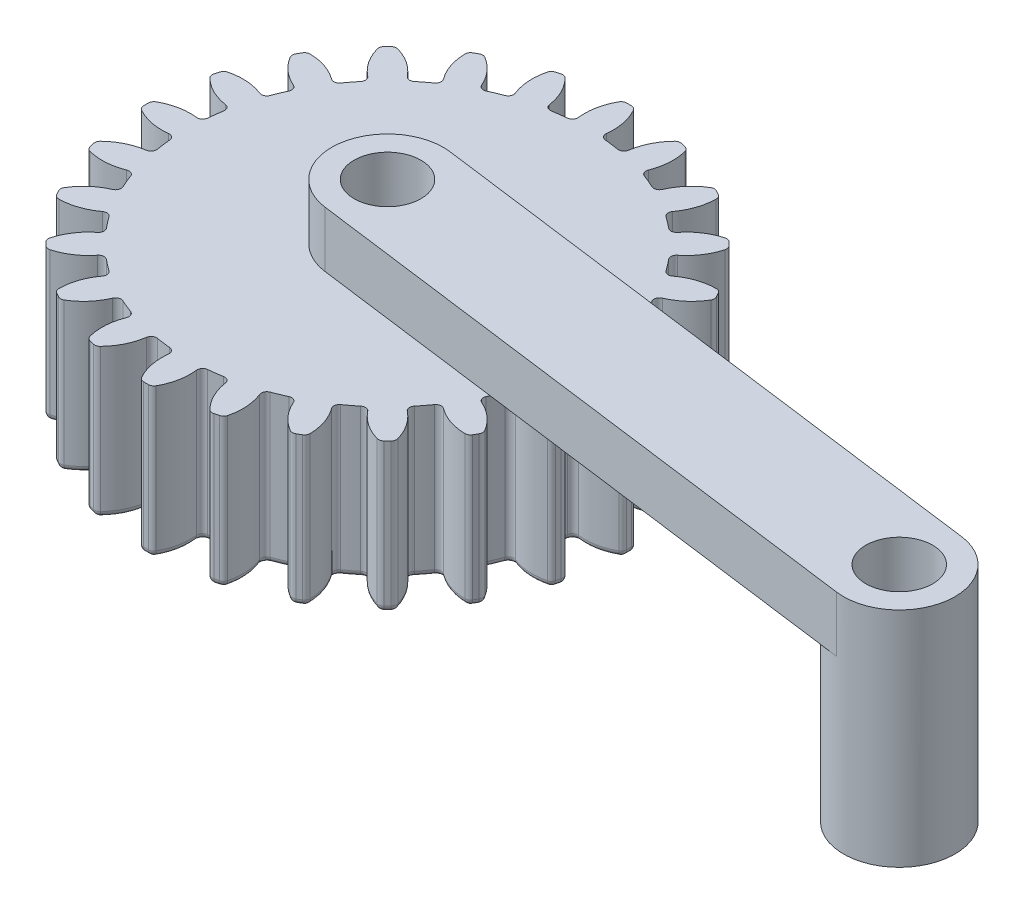
SolidWorks part; units mm, degrees
note: The reader was unsure of these and kept them because the rebuilt part matched: shared geometry of "Sketch2<5>".
ref_plane "Front Plane" through (0, 0, 0) normal (0, 0, 1) x (1, 0, 0)
ref_plane "Top Plane" through (0, 0, 0) normal (0, 1, 0) x (1, 0, 0)
ref_plane "Right Plane" through (0, 0, 0) normal (1, 0, 0) x (0, 0, -1)
sketch "Sketch2" plane through (0, 0, 0) normal (0, 1, 0) x (1, 0, 0)
  line L0 (0, 0) -> (0, 10.4648) construction
  line L1 (0.3, 13) -> (-0.3, 13)
  circle A0 centre (0, 0) radius 10.75
  circle A1 centre (0, 0) radius 13 construction
  arc A2 (-0.3, 13) -> (-0.7, 10.7272) centre (2.2248, 11.3841) ccw
  arc A3 (0.3, 13) -> (0.7, 10.7272) centre (-2.2248, 11.3841) cw
  circle A4 centre (0, 0) radius 2.55
  arc A5 (-0.7, 10.7272) -> (0.7, 10.7272) centre (0, 0) cw
  point P10 (0, 13)
  dimension "D1" = 21.5
  dimension "D2" = 26
  dimension "D5" = 5.1
  dimension "D3" = 0.6
  dimension "D4" = 0.7
extrude "Boss-Extrude1" add sketch "Sketch2" along normal blind 8
extrude "Boss-Extrude2" add sketch "Sketch2<5>" along normal blind 8 contours A3 L1 A2 A0
sketch "Sketch2<5>" plane through (0, 0, 0) normal (0, 1, 0) x (1, 0, 0) same geometry as "Sketch2"
pattern_circular "CirPattern2" count 24 over 360 about axis through (0, 0, 0) along (0, 1, 0) of "Boss-Extrude2"
sketch "Sketch3" plane through (0, 8, 0) normal (0, 1, 0) x (1, 0, 0)
  line L0 (31.7262, -4.1768) -> (0, 0) construction
  line L1 (31.3347, -7.1512) -> (-0.3916, -2.9743)
  line L2 (32.1178, -1.2025) -> (0.3916, 2.9743)
  line L3 (0, 0) -> (16.4404, 0) construction
  line L4 (0, 0) -> (14.8691, -3.9842) construction
  line L5 (12.4794, -3.6544) -> (12.6347, -3.0749) construction
  line L6 (12.6347, -3.0749) -> (12.557, -3.3646) construction
  arc A0 (31.3347, -7.1512) -> (32.1178, -1.2025) centre (31.7262, -4.1768) ccw
  arc A1 (0.3916, 2.9743) -> (-0.3916, -2.9743) centre (0, 0) ccw
  circle A2 centre (0, 0) radius 1.8
  circle A3 centre (31.7262, -4.1768) radius 1.8
  point P2 (15.8631, -2.0884)
  dimension "D1" = 3
  dimension "D3" = 3.6
  dimension "D2" = 32
  dimension "D4" = 15
  dimension "D5" = 7.5
extrude "Boss-Extrude3" add sketch "Sketch3" along normal blind 3
sketch "Sketch4" plane through (0, 8, 0) normal (0, -1, 0) x (1, 0, 0)
  circle A0 centre (31.7262, 4.1768) radius 1.8
  circle A1 centre (31.7262, 4.1768) radius 3
  dimension "D1" = 3.6
extrude "Boss-Extrude4" add sketch "Sketch4" along normal blind 9
sketch "Sketch5" plane through (0, 8, 0) normal (0, -1, 0) x (1, 0, 0)
  circle A0 centre (0, 0) radius 1.8
  circle A1 centre (0, 0) radius 2.55
  dimension "D1" = 3.6
extrude "Boss-Extrude5" add sketch "Sketch5" along normal blind 3
fillet "Fillet1" radius 0.3 96 edges at (4.7574, 4, 9.64) (6.2402, 4, 11.4083) (6.7598, 4, 11.1083) (5.9698, 4, 8.94) (2.1003, 4, 10.5428) (3.0749, 4, 12.6347) (3.6544, 4, 12.4794) (3.4525, 4, 10.1805) (-0.7, 4, 10.7272) (-0.3, 4, 13) (0.3, 4, 13) (0.7, 4, 10.7272) (0.7, 4, -10.7272) (-3.4525, 4, 10.1805) (-3.6544, 4, 12.4794) (-3.0749, 4, 12.6347) (-2.1003, 4, 10.5428) (0.3, 4, -13) (-0.3, 4, -13) (-5.9698, 4, 8.94) (-6.7598, 4, 11.1083) (-6.2402, 4, 11.4083) (-4.7574, 4, 9.64) (-0.7, 4, -10.7272) (-8.0802, 4, 7.0903) (-9.4045, 4, 8.9803) (-8.9803, 4, 9.4045) (-7.0903, 4, 8.0802) (-9.64, 4, 4.7574) (-11.4083, 4, 6.2402) (-11.1083, 4, 6.7598) (-8.94, 4, 5.9698) (-10.5428, 4, 2.1003) (-12.6347, 4, 3.0749) (-12.4794, 4, 3.6544) (-10.1805, 4, 3.4525) (-10.7272, 4, -0.7) (-13, 4, -0.3) (-13, 4, 0.3) (-10.7272, 4, 0.7) (-10.1805, 4, -3.4525) (-12.4794, 4, -3.6544) (-12.6347, 4, -3.0749) (-10.5428, 4, -2.1003) (-8.94, 4, -5.9698) (-11.1083, 4, -6.7598) (-11.4083, 4, -6.2402) (-9.64, 4, -4.7574) (-7.0903, 4, -8.0802) (-8.9803, 4, -9.4045) (-9.4045, 4, -8.9803) (-8.0802, 4, -7.0903) (-4.7574, 4, -9.64) (-6.2402, 4, -11.4083) (-6.7598, 4, -11.1083) (-5.9698, 4, -8.94) (10.7272, 4, 0.7) (13, 4, 0.3) (13, 4, -0.3) (10.7272, 4, -0.7) (10.5428, 4, -2.1003) (12.6347, 4, -3.0749) (12.4794, 4, -3.6544) (10.1805, 4, -3.4525) (9.64, 4, -4.7574) (11.4083, 4, -6.2402) (11.1083, 4, -6.7598) (8.94, 4, -5.9698) (8.0802, 4, -7.0903) (9.4045, 4, -8.9803) (8.9803, 4, -9.4045) (7.0903, 4, -8.0802) (5.9698, 4, -8.94) (6.7598, 4, -11.1083) (6.2402, 4, -11.4083) (4.7574, 4, -9.64) (3.4525, 4, -10.1805) (3.6544, 4, -12.4794) (3.0749, 4, -12.6347) (2.1003, 4, -10.5428) (-2.1003, 4, -10.5428) (-3.0749, 4, -12.6347) (-3.6544, 4, -12.4794) (-3.4525, 4, -10.1805) (10.1805, 4, 3.4525) (12.4794, 4, 3.6544) (12.6347, 4, 3.0749) (10.5428, 4, 2.1003) (8.94, 4, 5.9698) (11.1083, 4, 6.7598) (11.4083, 4, 6.2402) (9.64, 4, 4.7574) (7.0903, 4, 8.0802) (8.9803, 4, 9.4045) (9.4045, 4, 8.9803) (8.0802, 4, 7.0903)
fillet "Fillet2" radius 0.3 192 edges at (-4.6982, 0, 9.7715) (-3.5874, 0, 10.2316) (-2.009, 0, 10.6545) (-0.817, 0, 10.8115) (0.817, 0, 10.8115) (2.009, 0, 10.6545) (3.5874, 0, 10.2316) (4.6982, 0, 9.7715) (6.1133, 0, 8.9545) (7.0671, 0, 8.2226) (8.2226, 0, 7.0671) (8.9545, 0, 6.1133) (9.7715, 0, 4.6982) (10.2316, 0, 3.5874) (10.6545, 0, 2.009) (10.8115, 0, 0.817) (10.8115, 0, -0.817) (10.6545, 0, -2.009) (10.2316, 0, -3.5874) (9.7715, 0, -4.6982) (8.9545, 0, -6.1133) (8.2226, 0, -7.0671) (7.0671, 0, -8.2226) (6.1133, 0, -8.9545) (4.6982, 0, -9.7715) (3.5874, 0, -10.2316) (2.009, 0, -10.6545) (0.817, 0, -10.8115) (-0.817, 0, -10.8115) (-2.009, 0, -10.6545) (-3.3646, 0, -12.557) (-1.4032, 0, -10.658) (-0.7152, 0, -11.9691) (0, 0, -13) (0.7152, 0, -11.9691) (1.4032, 0, -10.658) (2.407, 0, -11.7464) (3.3646, 0, -12.557) (3.7887, 0, -11.3761) (4.1138, 0, -9.9317) (5.3651, 0, -10.7231) (6.5, 0, -11.2583) (6.6039, 0, -10.0079) (6.5442, 0, -8.5285) (7.9577, 0, -8.9691) (9.1924, 0, -9.1924) (8.9691, 0, -7.9577) (8.5285, 0, -6.5442) (10.0079, 0, -6.6039) (11.2583, 0, -6.5) (10.7231, 0, -5.3651) (9.9317, 0, -4.1138) (11.3761, 0, -3.7887) (12.557, 0, -3.3646) (11.7464, 0, -2.407) (10.658, 0, -1.4032) (11.9691, 0, -0.7152) (13, 0, 0) (11.9691, 0, 0.7152) (10.658, 0, 1.4032) (11.7464, 0, 2.407) (12.557, 0, 3.3646) (11.3761, 0, 3.7887) (9.9317, 0, 4.1138) (10.7231, 0, 5.3651) (11.2583, 0, 6.5) (10.0079, 0, 6.6039) (8.5285, 0, 6.5442) (8.9691, 0, 7.9577) (9.1924, 0, 9.1924) (7.9577, 0, 8.9691) (6.5442, 0, 8.5285) (6.6039, 0, 10.0079) (6.5, 0, 11.2583) (5.3651, 0, 10.7231) (4.1138, 0, 9.9317) (3.7887, 0, 11.3761) (3.3646, 0, 12.557) (2.407, 0, 11.7464) (1.4032, 0, 10.658) (0.7152, 0, 11.9691) (0, 0, 13) (-0.7152, 0, 11.9691) (-1.4032, 0, 10.658) (-2.407, 0, 11.7464) (-3.3646, 0, 12.557) (-3.7887, 0, 11.3761) (-4.1138, 0, 9.9317) (-5.3651, 0, 10.7231) (-6.5, 0, 11.2583) (-6.6039, 0, 10.0079) (-6.5442, 0, 8.5285) (-7.9577, 0, 8.9691) (-9.1924, 0, 9.1924) (-8.9691, 0, 7.9577) (-8.5285, 0, 6.5442) (-10.0079, 0, 6.6039) (-11.2583, 0, 6.5) (-10.7231, 0, 5.3651) (-9.9317, 0, 4.1138) (-11.3761, 0, 3.7887) (-12.557, 0, 3.3646) (-11.7464, 0, 2.407) (-10.658, 0, 1.4032) (-11.9691, 0, 0.7152) (-13, 0, 0) (-11.9691, 0, -0.7152) (-10.658, 0, -1.4032) (-11.7464, 0, -2.407) (-12.557, 0, -3.3646) (-11.3761, 0, -3.7887) (-9.9317, 0, -4.1138) (-10.7231, 0, -5.3651) (-11.2583, 0, -6.5) (-10.0079, 0, -6.6039) (-8.5285, 0, -6.5442) (-8.9691, 0, -7.9577) (-9.1924, 0, -9.1924) (-7.9577, 0, -8.9691) (-6.5442, 0, -8.5285) (-6.6039, 0, -10.0079) (-6.5, 0, -11.2583) (-5.3651, 0, -10.7231) (-4.1138, 0, -9.9317) (-3.7887, 0, -11.3761) (-2.407, 0, -11.7464) (-0.2819, 0, -12.9588) (0.2819, 0, -12.9588) (3.0817, 0, -12.5902) (3.6263, 0, -12.4442) (6.2352, 0, -11.3636) (6.7235, 0, -11.0816) (8.9639, 0, -9.3626) (9.3626, 0, -8.9639) (11.0816, 0, -6.7235) (11.3636, 0, -6.2352) (12.4442, 0, -3.6263) (12.5902, 0, -3.0817) (12.9588, 0, -0.2819) (12.9588, 0, 0.2819) (12.5902, 0, 3.0817) (12.4442, 0, 3.6263) (11.3636, 0, 6.2352) (11.0816, 0, 6.7235) (9.3626, 0, 8.9639) (8.9639, 0, 9.3626) (6.7235, 0, 11.0816) (6.2352, 0, 11.3636) (3.6263, 0, 12.4442) (3.0817, 0, 12.5902) (0.2819, 0, 12.9588) (-0.2819, 0, 12.9588) (-3.0817, 0, 12.5902) (-3.6263, 0, 12.4442) (-6.2352, 0, 11.3636) (-6.7235, 0, 11.0816) (-8.9639, 0, 9.3626) (-9.3626, 0, 8.9639) (-11.0816, 0, 6.7235) (-11.3636, 0, 6.2352) (-12.4442, 0, 3.6263) (-12.5902, 0, 3.0817) (-12.9588, 0, 0.2819) (-12.9588, 0, -0.2819) (-12.5902, 0, -3.0817) (-12.4442, 0, -3.6263) (-11.3636, 0, -6.2352) (-11.0816, 0, -6.7235) (-9.3626, 0, -8.9639) (-8.9639, 0, -9.3626) (-6.7235, 0, -11.0816) (-6.2352, 0, -11.3636) (-3.6263, 0, -12.4442) (-3.0817, 0, -12.5902) (-3.5874, 0, -10.2316) (-4.6982, 0, -9.7715) (-6.1133, 0, -8.9545) (-7.0671, 0, -8.2226) (-8.2226, 0, -7.0671) (-8.9545, 0, -6.1133) (-9.7715, 0, -4.6982) (-10.2316, 0, -3.5874) (-10.6545, 0, -2.009) (-10.8115, 0, -0.817) (-10.8115, 0, 0.817) (-10.6545, 0, 2.009) (-10.2316, 0, 3.5874) (-9.7715, 0, 4.6982) (-8.9545, 0, 6.1133) (-8.2226, 0, 7.0671) (-7.0671, 0, 8.2226) (-6.1133, 0, 8.9545)
sketch "Sketch6" plane through (0, 0, 0) normal (0, -1, 0) x (1, 0, 0)
  circle A0 centre (0, 0) radius 3
  circle A1 centre (0, 0) radius 1.8
  dimension "D1" = 6
  dimension "D2" = 3.6
extrude "Boss-Extrude6" add sketch "Sketch6" along normal blind 1
